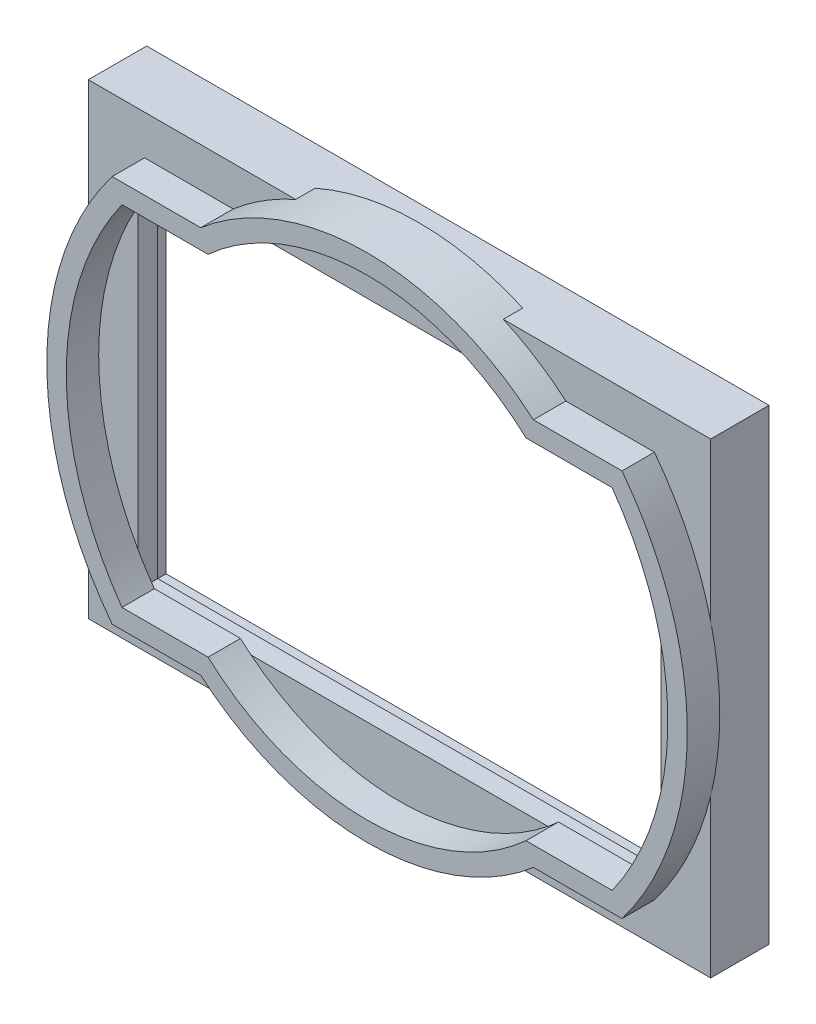
SolidWorks part; units mm, degrees
ref_plane "前视基准面" through (0, 0, 0) normal (0, 0, 1) x (1, 0, 0)
ref_plane "上视基准面" through (0, 0, 0) normal (0, 1, 0) x (1, 0, 0)
ref_plane "右视基准面" through (0, 0, 0) normal (1, 0, 0) x (0, 0, -1)
other "Configuration Table"
sketch "草图1" plane through (0, 0, 0) normal (0, 0, 1) x (1, 0, 0)
  line L0 (-18.9034, 13.45) -> (-12.2612, 13.45)
  line L1 (18.9034, 13.45) -> (-18.9034, -13.45) construction
  line L2 (-18.9034, -13.45) -> (-12.2612, -13.45)
  line L3 (12.2612, 13.45) -> (18.9034, 13.45)
  line L4 (12.2612, -13.45) -> (18.9034, -13.45)
  line L5 (-19.6618, 14.95) -> (-12.8292, 14.95)
  line L6 (12.8292, 14.95) -> (19.6618, 14.95)
  line L7 (12.8292, -14.95) -> (19.6618, -14.95)
  line L8 (-19.6618, -14.95) -> (-12.8292, -14.95)
  arc A0 (-18.9034, 13.45) -> (-18.9034, -13.45) centre (0, 0) ccw
  arc A1 (-12.2612, -13.45) -> (12.2612, -13.45) centre (0, 0) ccw
  arc A2 (12.2612, 13.45) -> (-12.2612, 13.45) centre (0, 0) ccw
  arc A3 (18.9034, -13.45) -> (18.9034, 13.45) centre (0, 0) ccw
  arc A4 (12.8292, 14.95) -> (-12.8292, 14.95) centre (0, 0) ccw
  arc A5 (19.6618, -14.95) -> (19.6618, 14.95) centre (0, 0) ccw
  arc A6 (-12.8292, -14.95) -> (12.8292, -14.95) centre (0, 0) ccw
  arc A7 (-19.6618, 14.95) -> (-19.6618, -14.95) centre (0, 0) ccw
  dimension "D1" = 36.4
  dimension "D2" = 46.4
  dimension "D3" = 26.9
  dimension "D4" = 1.5
extrude "凸台-拉伸1" add sketch "草图1" along normal blind 2.5
sketch "草图3" plane through (0, 0, 0) normal (0, 0, -1) x (-1, 0, 0)
  line L1 (-21.5, -15.5) -> (21.5, -15.5)
  line L2 (-21.5, -15.5) -> (-21.5, 15.5)
  line L3 (-21.5, 15.5) -> (21.5, 15.5)
  line L4 (21.5, -15.5) -> (21.5, 15.5)
  line L5 (-21.5, -15.5) -> (21.5, 15.5) construction
  line L6 (-21.5, 15.5) -> (21.5, -15.5) construction
  line L7 (-20.15, -14.15) -> (20.15, -14.15)
  line L8 (-20.15, -14.15) -> (-20.15, 14.15)
  line L9 (-20.15, 14.15) -> (20.15, 14.15)
  line L10 (20.15, -14.15) -> (20.15, 14.15)
  line L11 (-20.15, -14.15) -> (20.15, 14.15) construction
  line L12 (-20.15, 14.15) -> (20.15, -14.15) construction
  point P0 (0, 0)
  point P6 (0, 0)
  arc M3 (19.6618, -14.95) -> (19.6618, 14.95) centre (0, 0) ccw
  line M4 (19.6618, 14.95) -> (12.8292, 14.95)
  arc M5 (12.8292, 14.95) -> (-12.8292, 14.95) centre (0, 0) ccw
  line M6 (-12.8292, 14.95) -> (-19.6618, 14.95)
  arc M7 (-19.6618, 14.95) -> (-19.6618, -14.95) centre (0, 0) ccw
  line M8 (-19.6618, -14.95) -> (-12.8292, -14.95)
  arc M9 (-12.8292, -14.95) -> (12.8292, -14.95) centre (0, 0) ccw
  line M10 (12.8292, -14.95) -> (19.6618, -14.95)
  arc M11 (-12.2612, 13.45) -> (12.2612, 13.45) centre (0, 0) cw
  arc M13 (18.9034, 13.45) -> (18.9034, -13.45) centre (0, 0) cw
  arc M15 (12.2612, -13.45) -> (-12.2612, -13.45) centre (0, 0) cw
  arc M17 (-18.9034, -13.45) -> (-18.9034, 13.45) centre (0, 0) cw
  dimension "D1" = 43
  dimension "D2" = 31
  dimension "D3" = 40.3
  dimension "D4" = 28.3
extrude "凸台-拉伸2" add sketch "草图3" along normal blind 1.5 contours L3 L2 M7 M6 M5 | L8 L9 L3 L2 M11 M5 M6 M7 M17 | L9 L3 M11 | L3 M11 | L3 M5 M11 | L10 L4 L3 L9 M13 M3 M4 M5 M11 | L4 L3 M3 M5 M4 | L10 L4 M13 | L4 M3 M13 | L4 M13 | L10 L7 L1 L4 M15 M9 M10 M3 M13 | L1 L4 M3 M10 M9 | L7 L1 M15 | L1 M9 M15 | L1 M15 | L7 L8 L2 L1 M17 M7 M8 M9 M15 | L2 L1 M9 M8 M7 | L2 M7 M17 | L8 L2 M17 | L2 M17 region at (21.4008, -13.8295, 0) region at (12.4099, -15.1224, 0) region at (10.8489, -15.7468, 0) region at (24.4547, 0, 0) region at (0, -14.8047, 0) region at (0, -16.5872, 0) region at (-12.56, -15.3054, 0) region at (-10.8489, -15.3625, 0) region at (22.1822, 0, 0) region at (20.7944, 0, 0) region at (20.5133, 13.51, 0) region at (21.4008, 13.8295, 0) region at (-21.7453, -10.4381, 0) region at (0, 19.4532, 0) region at (-20.7944, 0, 0) region at (-22.1822, 0, 0) region at (-20.711, 13.6402, 0) region at (-21.3625, 10.4381, 0) region at (0, 16.5872, 0) region at (0, 14.8047, 0)
sketch "草图4" plane through (0, 0, -1.5) normal (0, 0, -1) x (-1, 0, 0)
  line L1 (-22.5, -16.5) -> (22.5, -16.5)
  line L2 (-22.5, -16.5) -> (-22.5, 16.5)
  line L3 (-22.5, 16.5) -> (22.5, 16.5)
  line L4 (22.5, -16.5) -> (22.5, 16.5)
  line L5 (-22.5, -16.5) -> (22.5, 16.5) construction
  line L6 (-22.5, 16.5) -> (22.5, -16.5) construction
  line L7 (-24, -18) -> (24, -18)
  line L8 (-24, -18) -> (-24, 18)
  line L9 (-24, 18) -> (24, 18)
  line L10 (24, -18) -> (24, 18)
  line L11 (-24, -18) -> (24, 18) construction
  line L12 (-24, 18) -> (24, -18) construction
  point P0 (0, 0)
  point P6 (0, 0)
  arc M6 (-12.1589, -15.5) -> (12.1589, -15.5) centre (0, 0) ccw
  line M7 (12.1589, -15.5) -> (21.5, -15.5)
  line M8 (21.5, -15.5) -> (21.5, -12.1589)
  arc M9 (21.5, -12.1589) -> (21.5, 12.1589) centre (0, 0) ccw
  line M10 (21.5, 12.1589) -> (21.5, 15.5)
  line M11 (21.5, 15.5) -> (12.1589, 15.5)
  arc M12 (12.1589, 15.5) -> (-12.1589, 15.5) centre (0, 0) ccw
  line M13 (-12.1589, 15.5) -> (-21.5, 15.5)
  line M14 (-21.5, 15.5) -> (-21.5, 12.1589)
  arc M15 (-21.5, 12.1589) -> (-21.5, -12.1589) centre (0, 0) ccw
  line M16 (-21.5, -12.1589) -> (-21.5, -15.5)
  line M17 (-21.5, -15.5) -> (-12.1589, -15.5)
  dimension "D1" = 45
  dimension "D2" = 33
  dimension "D3" = 48
  dimension "D4" = 36
extrude "凸台-拉伸3" add sketch "草图4" along normal blind 3
extrude "凸台-拉伸4" add sketch "草图4<2>" against normal blind 1.5 contours L10 L9 L3 L4 M9 M12 | L4 L3 M9 M12 M11 M10 | L9 L8 L2 L3 M15 M12 | L3 L2 M15 M14 M13 M12 | L2 L1 M6 M17 M16 M15 | L8 L7 L1 L2 M6 M15 | L1 L4 M9 M8 M7 M6 | L7 L10 L4 L1 M9 M6 region at (22.3667, -13.3451, -1.5) region at (16.6314, -16.7009, -1.5) region at (-11.5494, -16.1236, -1.5) region at (-16.6314, -16.7009, -1.5) region at (23.5415, 8.1149, -1.5) region at (22.3667, 13.3451, -1.5) region at (-22.1408, 11.2461, -1.5) region at (-22.7009, 13.3451, -1.5)
sketch "草图4<2>" plane through (0, 0, -1.5) normal (0, 0, -1) x (-1, 0, 0) same geometry as "草图4"
extrude "切除-拉伸1" cut sketch "草图4<3>" against normal blind 1.5 contours L8 M15 | L10 M9 region at (24.2803, 0, -1.5) region at (-24.2803, 0, -1.5)
sketch "草图4<3>" plane through (0, 0, -1.5) normal (0, 0, -1) x (-1, 0, 0) same geometry as "草图4"
